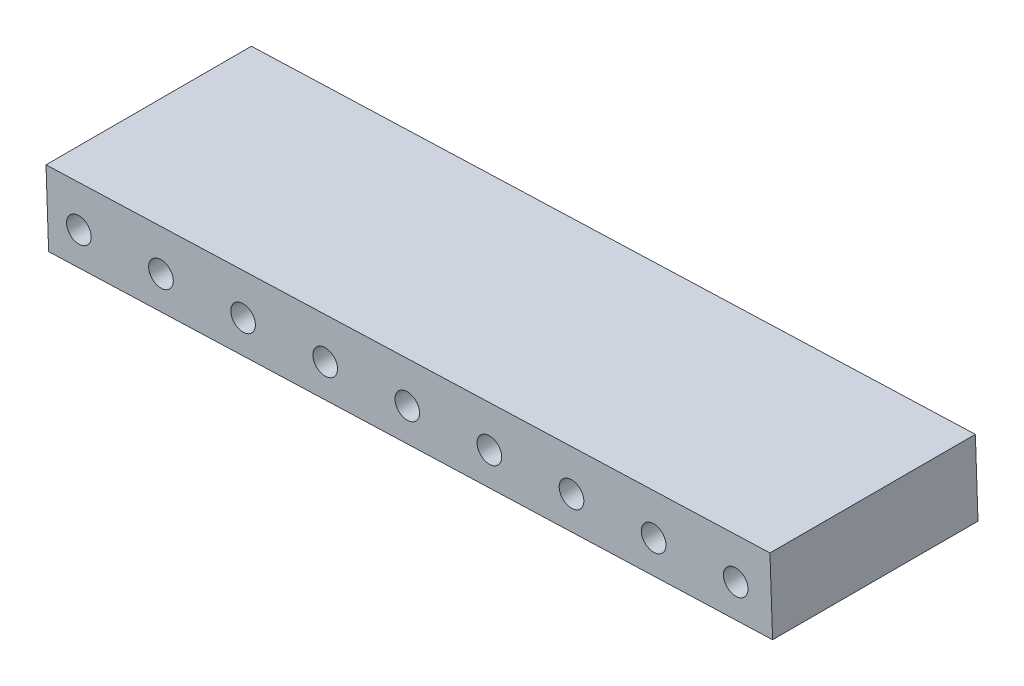
SolidWorks part; units mm, degrees
ref_plane "前视基准面" through (0, 0, 0) normal (0, 0, 1) x (1, 0, 0)
ref_plane "上视基准面" through (0, 0, 0) normal (0, 1, 0) x (1, 0, 0)
ref_plane "右视基准面" through (0, 0, 0) normal (1, 0, 0) x (0, 0, -1)
other "Configuration Table"
sketch "草图1" plane through (0, 0, 0) normal (0, 0, 1) x (1, 0, 0)
  line L0 (0, 0) -> (140, 0)
  line L1 (0, 35) -> (140, 25)
  line L2 (0, -35) -> (140, -25)
  circle A0 centre (0, 0) radius 35
  circle A1 centre (140, 0) radius 25
  dimension "D1" = 70
  dimension "D3" = 50
  dimension "D2" = 140
extrude "凸台-拉伸3" add sketch "草图1" along normal blind 5 contours A0 L1 L2 | A1 L0 A0 L2 | A1 L1 A0 L0 | A1 region at (72.7482, 16.0498, 0) region at (-0.0004, 0, 0) region at (72.7482, -16.0498, 0) region at (122.8223, 17.1777, 0)
sketch "草图4" plane through (0, 0, 5) normal (0, 0, 1) x (1, 0, 0)
  line L1 (-5, -5) -> (5, -5)
  line L2 (-5, -5) -> (-5, 5)
  line L3 (-5, 5) -> (5, 5)
  line L4 (5, -5) -> (5, 5)
  line L5 (-5, -5) -> (5, 5) construction
  line L6 (-5, 5) -> (5, -5) construction
  line L7 (135, -5) -> (145, -5)
  line L8 (135, -5) -> (135, 5)
  line L9 (135, 5) -> (145, 5)
  line L10 (145, -5) -> (145, 5)
  line L11 (135, -5) -> (145, 5) construction
  line L12 (135, 5) -> (145, -5) construction
  circle A0 centre (0, 0) radius 4
  circle A1 centre (-5, 5) radius 1.5
  circle A2 centre (5, 5) radius 1.5
  circle A3 centre (5, -5) radius 1.5
  circle A4 centre (-5, -5) radius 1.5
  circle A5 centre (140, 0) radius 4
  circle A6 centre (135, 5) radius 1.5
  circle A7 centre (145, 5) radius 1.5
  circle A8 centre (145, -5) radius 1.5
  circle A9 centre (135, -5) radius 1.5
  dimension "D1" = 8
  dimension "D4" = 3
  dimension "D6" = 8
  dimension "D9" = 3
  dimension "D2" = 10
  dimension "D3" = 10
  dimension "D7" = 10
  dimension "D8" = 10
  dimension "D5" = 4
  dimension "D10" = 4
extrude "切除-拉伸3" cut sketch "草图4" against normal blind 5 contours A5 | A0 | L2 A4 L1 | L1 A4 L2 | A6 | A9 | A8 | A7 | A1 | A2 | A3 region at (-4.3634, -4.3634, 5) region at (-5.2122, -5.2122, 5) region at (0, 0, 5) region at (140, 0, 5)
sketch "草图5" plane through (0, 0, 5) normal (0, 0, 1) x (1, 0, 0)
  circle A0 centre (0, 0) radius 11
  circle A1 centre (140, 0) radius 11
  dimension "D1" = 22
  dimension "D2" = 22
extrude "切除-拉伸4" cut sketch "草图5" against normal blind 2
sketch "草图6" plane through (0, 0, 5) normal (0, 0, 1) x (1, 0, 0)
  circle A0 centre (0, 0) radius 30
  circle A1 centre (0, 30) radius 1.5
  circle A2 centre (15, 25.9808) radius 1.5
  circle A3 centre (25.9808, 15) radius 1.5
  circle A4 centre (30, 0) radius 1.5
  circle A5 centre (25.9808, -15) radius 1.5
  circle A6 centre (15, -25.9808) radius 1.5
  circle A7 centre (0, -30) radius 1.5
  circle A8 centre (-15, -25.9808) radius 1.5
  circle A9 centre (-25.9808, -15) radius 1.5
  circle A10 centre (-30, 0) radius 1.5
  circle A11 centre (-25.9808, 15) radius 1.5
  circle A12 centre (-15, 25.9808) radius 1.5
  circle A13 centre (140, 0) radius 20
  circle A14 centre (140, 20) radius 1.5
  circle A15 centre (150, 17.3205) radius 1.5
  circle A16 centre (157.3205, 10) radius 1.5
  circle A17 centre (160, 0) radius 1.5
  circle A18 centre (157.3205, -10) radius 1.5
  circle A19 centre (150, -17.3205) radius 1.5
  circle A20 centre (140, -20) radius 1.5
  circle A21 centre (130, -17.3205) radius 1.5
  circle A22 centre (122.6795, -10) radius 1.5
  circle A23 centre (120, 0) radius 1.5
  circle A24 centre (122.6795, 10) radius 1.5
  circle A25 centre (130, 17.3205) radius 1.5
  point P29 (0, 0)
  dimension "D1" = 60
  dimension "D2" = 3
  dimension "D4" = 40
  dimension "D5" = 3
  dimension "D3" = 12
  dimension "D6" = 12
extrude "切除-拉伸6" cut sketch "草图6" against normal through all contours A0 A12 | A11 | A12 | A1 | A2 | A3 | A4 | A5 | A6 | A7 | A8 | A9 | A10 | A25 | A14 | A15 | A16 | A17 | A18 | A19 | A20 | A21 | A22 | A23 | A24 region at (-14.6783, 25.4236, 5)
sketch "草图7" plane through (0, 0, 5) normal (0, 0, 1) x (1, 0, 0)
  line L0 (140, 25) -> (0, 20)
  line L1 (140, -25) -> (0, -20)
  circle A0 centre (0, 0) radius 20
  circle A1 centre (140, 0) radius 25
  circle M1 centre (15, -25.9808) radius 1.5
  circle M2 centre (0, -30) radius 1.5
  circle M3 centre (-15, -25.9808) radius 1.5
  circle M4 centre (-25.9808, -15) radius 1.5
  circle M5 centre (-30, 0) radius 1.5
  circle M20 centre (15, 25.9808) radius 1.5
  circle M21 centre (-15, 25.9808) radius 1.5
  circle M22 centre (-25.9808, 15) radius 1.5
  circle M23 centre (0, 30) radius 1.5
  line M27 (0, -35) -> (140, -25)
  line M29 (140, 25) -> (0, 35)
  arc M30 (0, 35) -> (0, -35) centre (0, 0) ccw
  dimension "D1" = 40
extrude "切除-拉伸7" cut sketch "草图7" against normal blind 10 contours A1 L1 A0 L0 M29 M30 M27 M1 M3 M5 M21 M23 M22 M20 M4 M2 region at (69.041, 24.3518, 5)
sketch "草图8" plane through (0, 0, 5) normal (0, 0, 1) x (1, 0, 0)
  circle A1 centre (0, 0) radius 11
extrude "切除-拉伸8" cut sketch "草图8" against normal blind 10
sketch "草图9" plane through (0, 0, 5) normal (0, 0, 1) x (1, 0, 0)
  circle A0 centre (0, 0) radius 15
  circle A1 centre (0, 15) radius 1.5
  circle A2 centre (10.6066, 10.6066) radius 1.5
  circle A3 centre (15, 0) radius 1.5
  circle A4 centre (10.6066, -10.6066) radius 1.5
  circle A5 centre (0, -15) radius 1.5
  circle A6 centre (-10.6066, -10.6066) radius 1.5
  circle A7 centre (-15, 0) radius 1.5
  circle A8 centre (-10.6066, 10.6066) radius 1.5
  dimension "D1" = 30
  dimension "D2" = 3
  dimension "D3" = 8
extrude "切除-拉伸9" cut sketch "草图9" against normal blind 10 contours A0 A4 | A2 | A3 | A4 | A5 | A6 | A7 | A8 | A1 region at (11.0471, -11.0471, 5)
sketch "草图10" plane through (0, 0, 3) normal (0, 0, 1) x (1, 0, 0)
  circle A0 centre (140, 0) radius 5
  dimension "D1" = 10
extrude "切除-拉伸10" cut sketch "草图10" against normal blind 10
sketch "草图11" plane through (0, 0, 5) normal (0, 0, 1) x (1, 0, 0)
  line L0 (140, 0) -> (110, 0)
  line L1 (140, 0) -> (130, 0)
  line L2 (110, 0) -> (105.5, 0)
  line L3 (150, -10) -> (110, -10)
  line L4 (150, -10) -> (150, 10)
  line L5 (150, 10) -> (110, 10)
  line L6 (110, -10) -> (110, 10)
  line L7 (150, -10) -> (110, 10) construction
  line L8 (150, 10) -> (110, -10) construction
  line L9 (105.5, 0) -> (105.5, 5)
  line L10 (130, -1000) -> (130, 49000) construction
  circle A0 centre (105.5, 5) radius 2
  circle A1 centre (105.5, -5) radius 2
  circle A2 centre (154.5, -5) radius 2
  circle A3 centre (154.5, 5) radius 2
  circle M14 centre (140, 0) radius 11
  circle M16 centre (122.6795, 10) radius 1.5
  circle M20 centre (120, 0) radius 1.5
  circle M21 centre (122.6795, -10) radius 1.5
  dimension "D6" = 4
  dimension "D1" = 30
  dimension "D2" = 10
  dimension "D3" = 20
  dimension "D4" = 4.5
  dimension "D5" = 5
extrude "切除-拉伸11" cut sketch "草图11" against normal blind 10 contours A0 | A1 | A3 | A2 | L6 L3 L0 M21 M14 M20 | L5 L3 L4 | L6 L0 L5 M20 M14 M16 | L4 L5 M14 | L3 L4 M14 region at (120.4472, -5.2396, 5) region at (120.4472, 5.2396, 5) region at (130.9864, 5.7844, 5) region at (104.1258, 6.3742, 5) region at (148.4191, 8.4191, 5) region at (148.4191, -8.4191, 5) region at (105.5, -5, 5) region at (154.5, -5, 5) region at (154.5, 5, 5)
sketch "草图12" plane through (0, 0, 5) normal (0, 0, 1) x (1, 0, 0)
  line L0 (110, 10) -> (44831.3595, -22350.6798) construction
  line L1 (150, 10) -> (-44571.3595, -22350.6798) construction
  line L3 (109.5, -11) -> (150.5, -11)
  line L4 (109.5, -11) -> (109.5, 11)
  line L5 (109.5, 11) -> (150.5, 11)
  line L6 (150.5, -11) -> (150.5, 11)
  line L7 (109.5, -11) -> (150.5, 11) construction
  line L8 (109.5, 11) -> (150.5, -11) construction
  point P8 (130, 0)
  dimension "D1" = 41
  dimension "D2" = 22
extrude "切除-拉伸12" cut sketch "草图12" against normal blind 10
sketch "草图13" plane through (0, 0, 5) normal (0, 0, 1) x (1, 0, 0)
  line L0 (0.1785, -15.0032) -> (138.395, -19.9395)
  line L1 (0, -20) -> (138.2166, -24.9363)
  circle A0 centre (0, -15) radius 1.5
  circle A1 centre (9.9936, -15.3569) radius 1.5
  circle A2 centre (19.9873, -15.7138) radius 1.5
  circle A3 centre (29.9809, -16.0707) radius 1.5
  circle A4 centre (39.9745, -16.4277) radius 1.5
  circle A5 centre (49.9681, -16.7846) radius 1.5
  circle A6 centre (59.9618, -17.1415) radius 1.5
  circle A7 centre (69.9554, -17.4984) radius 1.5
  circle A8 centre (79.949, -17.8553) radius 1.5
  circle A9 centre (89.9427, -18.2122) radius 1.5
  circle A10 centre (99.9363, -18.5692) radius 1.5
  circle A11 centre (109.9299, -18.9261) radius 1.5
  circle A12 centre (119.9235, -19.283) radius 1.5
  circle A13 centre (129.9172, -19.6399) radius 1.5
  circle A14 centre (139.9108, -19.9968) radius 1.5
  circle M27 centre (130, -17.3205) radius 1.5
  dimension "D1" = 5
  dimension "D2" = 15
extrude "切除-拉伸13" cut sketch "草图13" against normal blind 10 contours L0 A1 | L0 A1 | L0 A13 | A13 L0 M27 | A2 | A3 | A4 | A5 | A6 | A7 | A9 | A8 | A10 | A11 | A12 region at (129.9337, -19.1762, 5) region at (129.8945, -20.2744, 5) region at (10.0164, -14.719, 5) region at (9.971, -15.9914, 5)
sketch "草图14" plane through (0, 0, 5) normal (0, 0, 1) x (1, 0, 0)
  circle A0 centre (130, -17.3205) radius 1.5
  circle A1 centre (129.9172, -19.6399) radius 1.5
extrude "凸台-拉伸4" add sketch "草图14" against normal blind 5 contours A1 A0 region at (130.0059, -17.1551, 5)
sketch "草图15" plane through (0, 0, 5) normal (0, 0, 1) x (1, 0, 0)
  circle A0 centre (25.9808, 15) radius 1.5
  circle A1 centre (30, 0) radius 1.5
  circle A2 centre (25.9808, -15) radius 1.5
extrude "凸台-拉伸6" add sketch "草图15" against normal blind 5
sketch "草图16" plane through (0, 0, 5) normal (0, 0, 1) x (1, 0, 0)
  line L0 (0, 20) -> (140, 25)
  line L1 (0.1785, 15.0032) -> (140.1785, 20.0032)
  arc A0 (138.2166, -24.9363) -> (138.2166, 24.9363) centre (140, 0) ccw construction
  circle A1 centre (0, 15) radius 1.5
  circle A2 centre (9.9936, 15.3569) radius 1.5
  circle A3 centre (19.9873, 15.7138) radius 1.5
  circle A4 centre (29.9809, 16.0707) radius 1.5
  circle A5 centre (39.9745, 16.4277) radius 1.5
  circle A6 centre (49.9681, 16.7846) radius 1.5
  circle A7 centre (59.9618, 17.1415) radius 1.5
  circle A8 centre (69.9554, 17.4984) radius 1.5
  circle A9 centre (79.949, 17.8553) radius 1.5
  circle A10 centre (89.9427, 18.2122) radius 1.5
  circle A11 centre (99.9363, 18.5692) radius 1.5
  circle A12 centre (109.9299, 18.9261) radius 1.5
  circle A13 centre (119.9235, 19.283) radius 1.5
  circle A14 centre (129.9172, 19.6399) radius 1.5
  circle A15 centre (139.9108, 19.9968) radius 1.5
  dimension "D1" = 5
  dimension "D2" = 15
extrude "切除-拉伸14" cut sketch "草图16" against normal blind 5 contours L1 A6 | L1 A6 | L1 A7 | L1 A7 | L1 A8 | L1 A8 | A2 | A3 | A4 | A5 | A9 | A10 | A11 | A12 | A13 | A14 region at (69.9327, 18.1329, 5) region at (69.9782, 16.8605, 5) region at (59.9391, 17.776, 5) region at (59.9846, 16.5036, 5) region at (49.9455, 17.4191, 5) region at (49.9909, 16.1466, 5)
sketch "草图17" plane through (0, 0, 5) normal (0, 0, 1) x (1, 0, 0)
  circle A0 centre (130, 17.3205) radius 1.5
  circle A1 centre (129.9172, 19.6399) radius 1.5
extrude "凸台-拉伸7" add sketch "草图17" against normal blind 5 contours A1 A0 region at (130.0059, 17.1551, 5)
sketch "草图18" plane through (0, 0, 5) normal (0, 0, 1) x (1, 0, 0)
  line L2 (138.5735, 14.9427) -> (0.3569, 10.0064)
  line L3 (138.5735, 14.9427) -> (0.3569, 10.0064)
  line L5 (138.5735, -14.9427) -> (0.3569, -10.0064)
  line L6 (138.5735, -14.9427) -> (0.3569, -10.0064)
  circle A0 centre (0, 0) radius 25
  circle A1 centre (0, 0) radius 100
  dimension "D1" = 50
  dimension "D2" = 200
  dimension "D3" = 10
  dimension "D4" = 10
extrude "切除-拉伸15" cut sketch "草图18" against normal blind 5 contours L6 A1 L3 A0 region at (63.3314, 0, 5)
sketch "草图19" plane through (0, 0, 5) normal (0, 0, 1) x (1, 0, 0)
  line L2 (99.0445, 14.5316) -> (22.5117, 11.7983)
  line L3 (134.9707, 15.8146) -> (6.5499, 11.2282)
  line L4 (16.3089, 11.5767) -> (15.9877, 20.571)
  line L5 (99.0445, -14.5316) -> (22.5117, -11.7983)
  line L6 (134.4063, -15.7945) -> (10.6063, -11.3731)
  line L7 (138.2166, 24.9363) -> (0, 20) construction
  line L8 (16.3089, -11.5767) -> (15.9877, -20.571)
  line L9 (138.2166, -24.9363) -> (0, -20) construction
  line L10 (15.9877, -20.571) -> (0, -20)
  line L11 (15.9877, 20.571) -> (0, 20)
  circle A1 centre (140, 0) radius 16.7558
  circle A2 centre (0, 0) radius 20
  dimension "D1" = 1
  dimension "D2" = 1
extrude "切除-拉伸19" cut sketch "草图19" against normal blind 5 contours A2 | A2 L4 L11 | A2 L10 L8 | A1 | A2 L6 A1 L3 region at (75.0685, 0, 5) region at (140, 0, 5) region at (12.134, 17.8788, 5) region at (0, 0, 5) region at (12.134, -17.8788, 5)
sketch "草图21" plane through (0, 0, 5) normal (0, 0, 1) x (1, 0, 0)
  line L0 (134.4063, 15.7945) -> (134.0851, 24.7888)
  line L1 (138.2166, 24.9363) -> (15.9877, 20.571) construction
  line L2 (134.4063, -15.7945) -> (134.0851, -24.7888)
  line L3 (138.2166, -24.9363) -> (15.9877, -20.571) construction
  circle A0 centre (140, 0) radius 25
  arc M1 (156.2593, 4.0487) -> (156.2593, -4.0487) centre (140, 0) cw
  arc M2 (156.2593, -4.0487) -> (155.299, -6.8335) centre (154.5, -5) cw
  arc M3 (155.299, -6.8335) -> (134.4063, -15.7945) centre (140, 0) cw
  line M6 (15.9877, -20.571) -> (138.2166, -24.9363)
  arc M7 (138.2166, -24.9363) -> (138.2166, 24.9363) centre (140, 0) ccw
  line M8 (138.2166, 24.9363) -> (15.9877, 20.571)
  arc M11 (134.4063, 15.7945) -> (155.299, 6.8335) centre (140, 0) cw
  arc M12 (155.299, 6.8335) -> (156.2593, 4.0487) centre (154.5, 5) cw
  circle M37 centre (140, 20) radius 1.5
  circle M38 centre (150, 17.3205) radius 1.5
  circle M39 centre (157.3205, 10) radius 1.5
  circle M40 centre (160, 0) radius 1.5
  circle M41 centre (157.3205, -10) radius 1.5
  circle M42 centre (150, -17.3205) radius 1.5
  circle M43 centre (140, -20) radius 1.5
extrude "切除-拉伸20" cut sketch "草图21" against normal blind 5 contours A0 L0 L2 M7 M11 M12 M1 M2 M3 M38 M40 M42 M43 M41 M39 M37 | A0 L0 M8 | A0 L2 M6 region at (134.8419, 20.0655, 5) region at (135.2564, 24.6804, 5) region at (135.2564, -24.6804, 5)
sketch "草图22" plane through (0, 0, 0) normal (0, 0, -1) x (-1, 0, 0)
  line L0 (-134.0851, 24.7888) -> (-134.4063, 15.7945)
  line L1 (-134.4063, 15.7945) -> (-16.3089, 11.5767)
  line L2 (-16.3089, 11.5767) -> (-15.9877, 20.571)
  line L3 (-15.9877, 20.571) -> (-134.0851, 24.7888)
  line L4 (-134.4063, -15.7945) -> (-134.0851, -24.7888)
  line L5 (-134.0851, -24.7888) -> (-15.9877, -20.571)
  line L6 (-15.9877, -20.571) -> (-16.3089, -11.5767)
  line L7 (-16.3089, -11.5767) -> (-134.4063, -15.7945)
extrude "凸台-拉伸8" add sketch "草图22" along normal blind 10
sketch "草图23" plane through (0, 0, 5) normal (0, 0, 1) x (1, 0, 0)
  circle A0 centre (19.9873, 15.7138) radius 1.5
  circle A1 centre (29.9809, 16.0707) radius 1.5
  circle A2 centre (39.9745, 16.4277) radius 1.5
  circle A3 centre (49.9681, 16.7846) radius 1.5
  circle A4 centre (59.9618, 17.1415) radius 1.5
  circle A5 centre (69.9554, 17.4984) radius 1.5
  circle A6 centre (79.949, 17.8553) radius 1.5
  circle A7 centre (89.9427, 18.2122) radius 1.5
  circle A8 centre (99.9363, 18.5692) radius 1.5
  circle A9 centre (109.9299, 18.9261) radius 1.5
  circle A10 centre (119.9235, 19.283) radius 1.5
  circle A11 centre (129.9172, 19.6399) radius 1.5
  circle A12 centre (129.9172, -19.6399) radius 1.5
  circle A13 centre (119.9235, -19.283) radius 1.5
  circle A14 centre (109.9299, -18.9261) radius 1.5
  circle A15 centre (99.9363, -18.5692) radius 1.5
  circle A16 centre (89.9427, -18.2122) radius 1.5
  circle A17 centre (79.949, -17.8553) radius 1.5
  circle A18 centre (69.9554, -17.4984) radius 1.5
  circle A19 centre (59.9618, -17.1415) radius 1.5
  circle A20 centre (49.9681, -16.7846) radius 1.5
  circle A21 centre (39.9745, -16.4277) radius 1.5
  circle A22 centre (29.9809, -16.0707) radius 1.5
  circle A23 centre (19.9873, -15.7138) radius 1.5
extrude "切除-拉伸21" cut sketch "草图23" against normal blind 15
sketch "草图24" plane through (0, 0, -10) normal (0, 0, -1) x (-1, 0, 0)
  line L1 (-139.0544, 12.8066) -> (-138.879, 12.8066)
  line L2 (-139.0544, 12.8066) -> (-139.0544, -6.6664)
  line L3 (-139.0544, -6.6664) -> (-138.879, -6.6664)
  line L4 (-138.879, 12.8066) -> (-138.879, -6.6664)
  line L5 (-139.0544, 12.8066) -> (-138.879, -6.6664) construction
  line L6 (-139.0544, -6.6664) -> (-138.879, 12.8066) construction
  line L7 (-273.2608, -63.0482) -> (-10.2864, -63.0482)
  line L8 (-273.2608, -63.0482) -> (-273.2608, -7.8265)
  line L9 (-273.2608, -7.8265) -> (-10.2864, -7.8265)
  line L10 (-10.2864, -63.0482) -> (-10.2864, -7.8265)
  line L11 (-273.2608, -63.0482) -> (-10.2864, -7.8265) construction
  line L12 (-273.2608, -7.8265) -> (-10.2864, -63.0482) construction
  point P0 (-138.9667, 3.0701)
  point P5 (-141.7736, -35.4374)
extrude "切除-拉伸25" cut sketch "草图24" against normal through all both and the other way through all
sketch "草图25" plane through (0, 0, -10) normal (0, 0, -1) x (-1, 0, 0)
  line L0 (-134.0851, 24.7888) -> (-134.4063, 15.7945)
  line L1 (-134.4063, 15.7945) -> (-16.3089, 11.5767)
  line L2 (-16.3089, 11.5767) -> (-15.9877, 20.571)
  line L3 (-15.9877, 20.571) -> (-134.0851, 24.7888)
  line L4 (-129.9172, 19.6399) -> (49838.2255, -1764.9366) construction
  circle A0 centre (-129.9172, 19.6399) radius 1.5
  circle A1 centre (-119.9235, 19.283) radius 1.5
  circle A2 centre (-109.9299, 18.9261) radius 1.5
  circle A3 centre (-99.9363, 18.5692) radius 1.5
  circle A4 centre (-89.9427, 18.2122) radius 1.5
  circle A5 centre (-79.949, 17.8553) radius 1.5
  circle A6 centre (-69.9554, 17.4984) radius 1.5
  circle A7 centre (-59.9618, 17.1415) radius 1.5
  circle A8 centre (-49.9681, 16.7846) radius 1.5
  circle A9 centre (-39.9745, 16.4277) radius 1.5
  circle A10 centre (-29.9809, 16.0707) radius 1.5
  circle A11 centre (-19.9873, 15.7138) radius 1.5
  dimension "D1" = 12
extrude "凸台-拉伸9" add sketch "草图25" along normal blind 10
sketch "草图26" plane through (0, 0, -20) normal (0, 0, -1) x (-1, 0, 0)
  line L0 (-15.9877, 20.571) -> (-16.3089, 11.5767)
  line L1 (-23.9826, 20.8565) -> (-24.3038, 11.8623)
  line L4 (-33.9762, 21.2134) -> (-34.2974, 12.2192)
  line L5 (-33.9762, 21.2134) -> (-23.9826, 20.8565)
  line L6 (-34.2974, 12.2192) -> (-24.3038, 11.8623)
  line L7 (-134.0851, 24.7888) -> (-134.4063, 15.7945)
  line L8 (-114.0978, 24.0749) -> (-114.419, 15.0807)
  circle M10 centre (-129.9172, 19.6399) radius 1.5
  line M11 (-15.9877, 20.571) -> (-134.0851, 24.7888)
  line M12 (-134.0851, 24.7888) -> (-134.4063, 15.7945)
  line M13 (-134.4063, 15.7945) -> (-16.3089, 11.5767)
  circle M15 centre (-119.9235, 19.283) radius 1.5
  dimension "D2" = 10
  dimension "D1" = 8
  dimension "D3" = 20
extrude "切除-拉伸28" cut sketch "草图26" against normal through all both and the other way through all contours L8 M11 M12 M13 M10 M15 region at (124.1951, 19.975, -20)
sketch "草图27" plane through (0, 0, -20) normal (0, 0, -1) x (-1, 0, 0)
  line L0 (-16.3089, 11.5767) -> (-15.9877, 20.571)
  line L1 (-26.3025, 11.9336) -> (-25.9813, 20.9279)
  line L2 (-26.3025, 11.9336) -> (-16.3089, 11.5767)
  line L3 (-25.9813, 20.9279) -> (-15.9877, 20.571)
  dimension "D1" = 10
extrude "切除-拉伸29" cut sketch "草图27" against normal blind 25
